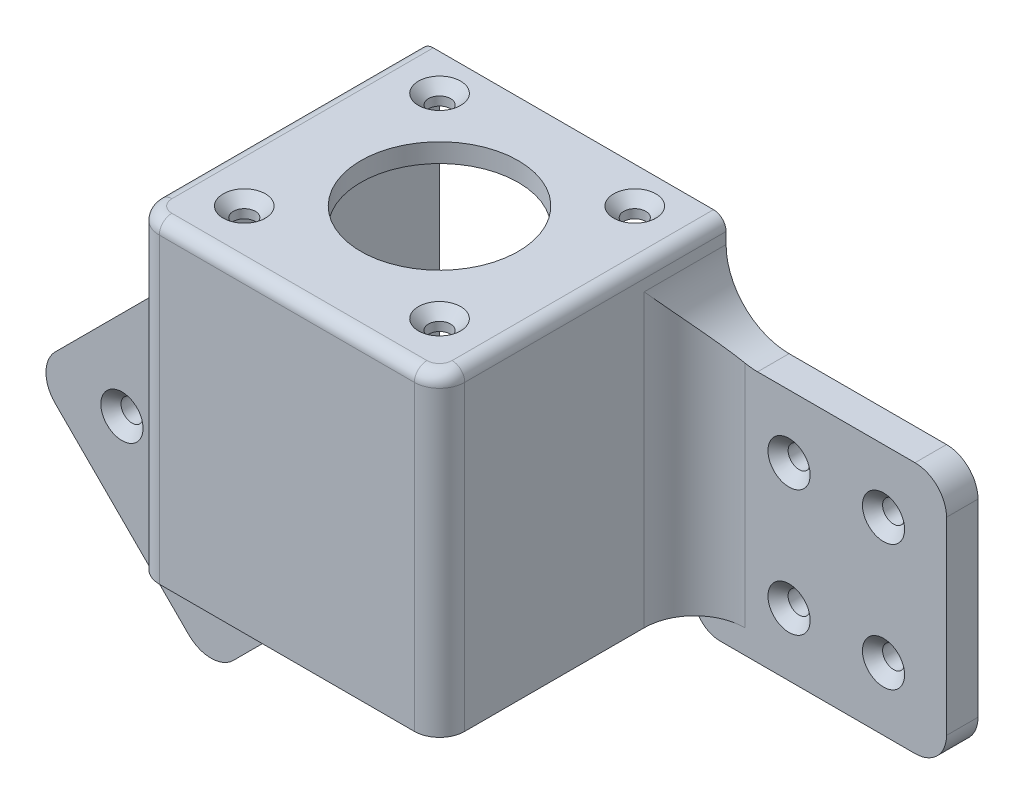
SolidWorks part; units mm, degrees
ref_plane "Front Plane" through (0, 0, 0) normal (0, 0, 1) x (1, 0, 0)
ref_plane "Top Plane" through (0, 0, 0) normal (0, 1, 0) x (1, 0, 0)
ref_plane "Right Plane" through (0, 0, 0) normal (1, 0, 0) x (0, 0, -1)
sketch "Sketch1" plane through (0, 0, 0) normal (0, 1, 0) x (1, 0, 0)
  line L0 (-24.25, 21.25) -> (-24.25, -24.25)
  line L1 (-21.25, 21.25) -> (21.25, 21.25) construction
  line L2 (-21.25, 21.25) -> (-21.25, -21.25) construction
  line L3 (-21.25, -21.25) -> (21.25, -21.25) construction
  line L4 (21.25, 21.25) -> (21.25, -21.25) construction
  line L5 (-21.25, 21.25) -> (21.25, -21.25) construction
  line L6 (-21.25, -21.25) -> (21.25, 21.25) construction
  line L7 (-24.25, -24.25) -> (24.25, -24.25)
  line L8 (24.25, 21.25) -> (24.25, -24.25)
  line L9 (-24.25, 21.25) -> (24.25, 21.25)
  point P0 (0, 0)
  dimension "D1" = 42.5
  dimension "D2" = 3
extrude "Boss-Extrude1" add sketch "Sketch1" along normal blind 3
sketch "Sketch2" plane through (0, 0, 0) normal (0, -1, 0) x (1, 0, 0)
  line L1 (-21.25, 21.25) -> (21.25, 21.25)
  line L2 (-21.25, 21.25) -> (-21.25, -21.25)
  line L4 (21.25, 21.25) -> (21.25, -21.25)
  line L5 (-21.25, 21.25) -> (21.25, -21.25) construction
  line L6 (-21.25, -21.25) -> (21.25, 21.25) construction
  line L7 (24.25, -21.25) -> (-24.25, -21.25) construction
  line L8 (21.25, -21.25) -> (24.25, -21.25)
  line L9 (-24.25, 24.25) -> (24.25, 24.25)
  line L10 (-24.25, 24.25) -> (-24.25, -21.25)
  line L11 (-24.25, -21.25) -> (-21.25, -21.25)
  line L12 (24.25, 24.25) -> (24.25, -21.25)
  point P0 (0, 0)
  dimension "D1" = 42.5
extrude "Boss-Extrude2" add sketch "Sketch2" along normal blind 47
sketch "Sketch3" plane through (24.25, 0, 0) normal (1, 0, 0) x (0, 0, -1)
  line L1 (21.25, -10.8) -> (16.25, -10.8)
  line L2 (21.25, -10.8) -> (21.25, -50.8)
  line L3 (21.25, -50.8) -> (16.25, -50.8)
  line L4 (16.25, -10.8) -> (16.25, -50.8)
  line L5 (21.25, 3) -> (21.25, -47) construction
  line L6 (-24.25, 3) -> (21.25, 3) construction
  dimension "D1" = 5
  dimension "D2" = 40
  dimension "D3" = 13.8
extrude "Boss-Extrude3" add sketch "Sketch3" along normal blind 40
sketch "Sketch4" plane through (0, 0, -21.25) normal (0, 0, -1) x (-1, 0, 0)
  line L0 (24.25, -10.8) -> (80.8185, -67.3685)
  line L1 (80.8185, -67.3685) -> (52.5343, -95.6528)
  line L2 (52.5343, -95.6528) -> (24.25, -67.3685)
  line L3 (24.25, 3) -> (24.25, -47) construction
  line L4 (24.25, -10.8) -> (24.25, -67.3685)
  dimension "D1" = 45
  dimension "D2" = 40
  dimension "D3" = 40
extrude "Boss-Extrude4" add sketch "Sketch4" against normal blind 5
fillet "Fillet1" radius 8 2 edges at (-24.25, -28.9, -16.25) (24.25, -28.9, -16.25)
sketch "Sketch5" plane through (0, 0, 0) normal (0, -1, 0) x (1, 0, 0)
  line L7 (-15.5, 15.5) -> (15.5, 15.5) construction
  line L8 (-15.5, 15.5) -> (-15.5, -15.5) construction
  line L9 (-15.5, -15.5) -> (15.5, -15.5) construction
  line L10 (15.5, 15.5) -> (15.5, -15.5) construction
  line L11 (-15.5, 15.5) -> (15.5, -15.5) construction
  line L12 (-15.5, -15.5) -> (15.5, 15.5) construction
  circle A0 centre (-15.5, 15.5) radius 1.75
  circle A1 centre (15.5, 15.5) radius 1.75
  circle A2 centre (15.5, -15.5) radius 1.75
  circle A3 centre (-15.5, -15.5) radius 1.75
  circle A4 centre (0, 0) radius 12.5
  point P0 (0, 0)
  dimension "D2" = 4
  dimension "D3" = 3.5
  dimension "D4" = 25
  dimension "D1" = 31
extrude "Cut-Extrude1" cut sketch "Sketch5" against normal through all
ref_plane "Plane1" through (0, -37, 0) normal (0, -1, 0) x (-1, 0, 0)
sketch "Sketch6" plane through (0, -37, 0) normal (0, -1, 0) x (-1, 0, 0)
  line L0 (24.25, 2.1079) -> (38.3921, 16.25)
  line L2 (80.8185, 16.25) -> (32.25, 16.25) construction
  line L3 (24.25, -24.25) -> (24.25, 8.25) construction
  line L4 (24.25, 16.25) -> (52.5343, 16.25) construction
  dimension "D1" = 45
  dimension "D2" = 20
sketch "Sketch7" plane through (0, 0, -16.25) normal (0, 0, 1) x (1, 0, 0)
  line L0 (54.25, -10.8) -> (54.25, -50.8) construction
  line L1 (64.25, -10.8) -> (32.25, -10.8) construction
  line L2 (64.25, -50.8) -> (24.25, -50.8) construction
  line L3 (-52.5343, -39.0843) -> (-24.25, -67.3685) construction
  line L4 (-80.8185, -67.3685) -> (-32.25, -18.8) construction
  line L5 (64.25, -50.8) -> (24.25, -50.8) construction
  line L6 (-52.5343, -95.6528) -> (-80.8185, -67.3685) construction
  line L7 (-52.5343, -39.0843) -> (-80.8185, -67.3685) construction
  line L8 (-73.7475, -60.2975) -> (-45.4632, -88.5817) construction
  line L9 (-24.25, -67.3685) -> (-52.5343, -95.6528) construction
  line L10 (-24.25, -67.3685) -> (-52.5343, -95.6528) construction
  line L11 (-66.6764, -67.3685) -> (-45.4632, -46.1553) construction
  line L12 (-52.5343, -81.5107) -> (-31.3211, -60.2975) construction
  line L13 (64.25, -10.8) -> (64.25, -50.8) construction
  line L14 (39.25, -10.8) -> (39.25, -50.8) construction
  circle A0 centre (54.25, -20.8) radius 1.75
  circle A1 centre (54.25, -40.8) radius 1.75
  circle A2 centre (-66.6764, -67.3685) radius 1.75
  circle A3 centre (-52.5343, -81.5107) radius 1.75
  circle A4 centre (-45.4632, -46.1553) radius 1.75
  circle A5 centre (-31.3211, -60.2975) radius 1.75
  circle A6 centre (39.25, -20.8) radius 1.75
  circle A7 centre (39.25, -40.8) radius 1.75
  point P42 (0, 0)
  point P43 (0, 0)
  point P44 (-73.7475, -60.2975)
  point P45 (0, 0)
  point P46 (0, 0)
  point P47 (-51.3881, -37.9381)
  point P48 (-24.25, -67.3685)
  dimension "D1" = 10
  dimension "D3" = 3.5
  dimension "D4" = 3.5
  dimension "D5" = 3.5
  dimension "D7" = 3.5
  dimension "D9" = 10
  dimension "D10" = 15
  dimension "D11" = 10
  dimension "D2" = 10
  dimension "D6" = 10
  dimension "D8" = 10
extrude "Cut-Extrude2" cut sketch "Sketch7" against normal through all
fillet "Fillet2" radius 10 3 edges at (24.25, -10.8, -14.75) (-24.25, -47, -18.75) (-24.25, -10.8, -14.75)
fillet "Fillet3" radius 5 5 edges at (64.25, -10.8, -18.75) (64.25, -50.8, -18.75) (-52.5343, -95.6528, -18.75) (-80.8185, -67.3685, -18.75) (-24.25, -67.3685, -18.75)
fillet "Fillet4" radius 2 2 edges at (21.25, -23.5, 21.25) (-21.25, -23.5, 21.25)
chamfer "Chamfer2" distance 1.6 angle 45 4 edges at (15.5, 3, -17.25) (15.5, 3, 13.75) (-15.5, 3, -17.25) (-15.5, 3, 13.75)
fillet "Fillet5" radius 4 1 edges at (24.25, -50.8, -18.75)
fillet "Fillet7" radius 4 2 edges at (24.25, -22, 24.25) (-24.25, -22, 24.25)
fillet "Fillet8" radius 2 5 edges at (24.25, 3, -0.5) (23.0784, 3, 23.0784) (0, 3, 24.25) (-23.0784, 3, 23.0784) (-24.25, 3, -0.5)
sketch "Sketch8" plane through (-24.25, 0, 0) normal (-1, 0, 0) x (0, 0, 1)
  line L0 (20.25, -47) -> (-8.25, -47) construction
  line L1 (-5, -47) -> (5, -47)
  line L2 (-5, -47) -> (-5, -37)
  line L3 (-5, -37) -> (5, -37)
  line L4 (5, -47) -> (5, -37)
  line L5 (21.25, -47) -> (-21.25, -47) construction
  line L6 (-21.25, -47) -> (-21.25, 0) construction
  line L7 (21.25, -47) -> (21.25, 0) construction
  point P13 (0, -47)
  dimension "D1" = 10
  dimension "D2" = 10
extrude "Cut-Extrude3" cut sketch "Sketch8" against normal up to next
fillet "Fillet9" radius 2 4 edges at (-22.75, -37, 5) (-22.75, -37, -5) (-22.75, -47, 5) (-22.75, -47, -5)
chamfer "Chamfer3" distance 1.6 angle 45 8 edges at (56, -40.8, -16.25) (56, -20.8, -16.25) (-50.7843, -81.5107, -16.25) (-64.9264, -67.3685, -16.25) (-29.5711, -60.2975, -16.25) (-43.7132, -46.1553, -16.25) (41, -40.8, -16.25) (41, -20.8, -16.25)
